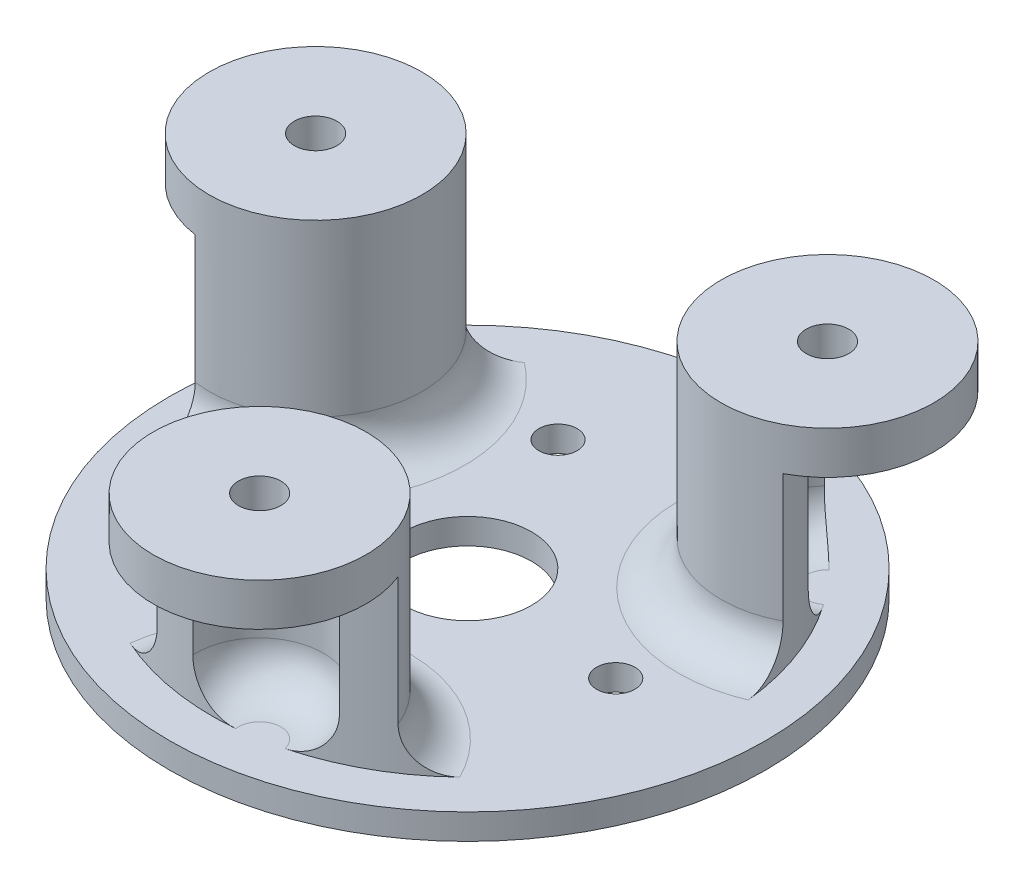
SolidWorks part; units mm, degrees
ref_plane "Front Plane" through (0, 0, 0) normal (0, 0, 1) x (1, 0, 0)
ref_plane "Top Plane" through (0, 0, 0) normal (0, 1, 0) x (1, 0, 0)
ref_plane "Right Plane" through (0, 0, 0) normal (1, 0, 0) x (0, 0, -1)
sketch "Sketch1" plane through (0, 0, 0) normal (0, 1, 0) x (1, 0, 0)
  line L0 (0, 0) -> (23.0264, 19.2298) construction
  line L1 (0, 0) -> (5.1402, -29.5564) construction
  line L2 (0, 0) -> (-28.1667, 10.3266) construction
  circle A0 centre (0, 0) radius 30
  circle A1 centre (-28.1667, 10.3266) radius 2.5
  circle A2 centre (23.0264, 19.2298) radius 2.5
  circle A3 centre (5.1402, -29.5564) radius 2.5
  circle A4 centre (5.1402, -29.5564) radius 12.5
  circle A5 centre (-28.1667, 10.3266) radius 12.5
  circle A6 centre (23.0264, 19.2298) radius 12.5
  circle A7 centre (5.1402, -29.5564) radius 7.5
  circle A8 centre (23.0264, 19.2298) radius 7.5
  circle A9 centre (-28.1667, 10.3266) radius 7.5
  point P10 (0, 0)
  point P13 (0, 0)
  point P14 (0, 0)
  point P15 (0, 0)
  dimension "D1" = 60
  dimension "D4" = 5
  dimension "D2" = 120
  dimension "D3" = 120
  dimension "D5" = 10
  dimension "D6" = 5
extrude "Boss-Extrude1" add sketch "Sketch1" along normal blind 5 contours A9 A0 A5 | A0 A9 A1 | A0 A9 A1 | A9 A0 A5 | A8 A0 A6 | A0 A8 A2 | A8 A0 A6 | A0 A8 A2 | A7 A0 A4 | A0 A7 A3 | A0 A7 A3 | A7 A0 A4 region at (13.6416, 0, -11.3923) region at (28.3744, 0, -10.6993) region at (17.1151, 0, 27.2405) region at (14.4442, 0, 25.9818) region at (20.2316, 0, -16.8958) region at (25.517, 0, -21.3096) region at (5.6962, 0, 32.7532) region at (4.5163, 0, 25.969) region at (-17.4634, 0, -16.2402) region at (-23.4449, 0, -19.2165) region at (-24.748, 0, -9.0732) region at (-31.2132, 0, -11.4435)
extrude "Boss-Extrude2" add sketch "Sketch1<3>" against normal blind 20 contours A9 A0 A5 | A8 A0 A6 | A7 A0 A4 region at (13.6416, 0, -11.3923) region at (14.4442, 0, 25.9818) region at (-17.4634, 0, -16.2402)
sketch "Sketch1<3>" plane through (0, 0, 0) normal (0, 1, 0) x (1, 0, 0) same geometry as "Sketch1"
sketch "Sketch3" plane through (0, -20, 0) normal (0, -1, 0) x (1, 0, 0)
  circle A0 centre (0, 0) radius 35
  dimension "D1" = 70
extrude "Boss-Extrude3" add sketch "Sketch3" along normal blind 3
sketch "Sketch4" plane through (0, -23, 0) normal (0, -1, 0) x (1, 0, 0)
  circle A0 centre (0, 0) radius 7.5
  dimension "D1" = 15
extrude "Cut-Extrude1" cut sketch "Sketch4" against normal blind 3
fillet "Fillet1" radius 5 6 edges at (-16.4306, -20, -6.0239) (13.4321, -20, -11.2174) (2.9985, -20, 17.2412) (-21.125, -20, -7.745) (3.8552, -20, 22.1673) (17.2698, -20, -14.4223)
sketch "Sketch5" plane through (0, -23, 0) normal (0, -1, 0) x (1, 0, 0)
  circle A0 centre (19.8487, 2.4552) radius 2.25 construction
  circle A1 centre (-7.7981, -18.4171) radius 2.25 construction
  circle A2 centre (-12.0506, 15.9619) radius 2.25 construction
  circle A3 centre (19.8487, 2.4552) radius 2.25
  circle A4 centre (-7.7981, -18.4171) radius 2.25
  circle A5 centre (-12.0506, 15.9619) radius 2.25
extrude "Cut-Extrude2" cut sketch "Sketch5" against normal blind 10
